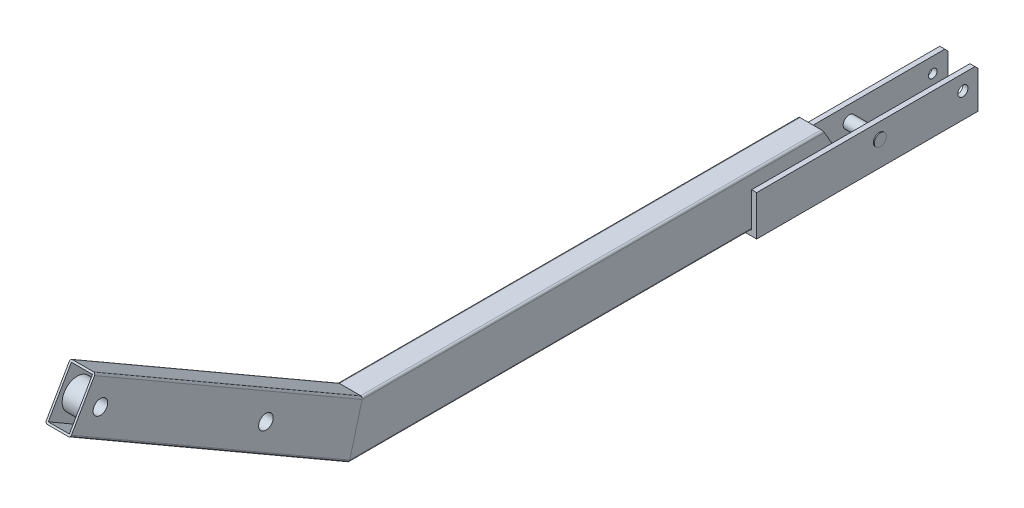
SolidWorks part; units mm, degrees
material "Structural Steel"
ref_plane "Piano frontale" through (0, 0, 0) normal (0, 0, 1) x (1, 0, 0)
ref_plane "Piano superiore" through (0, 0, 0) normal (0, 1, 0) x (1, 0, 0)
ref_plane "Piano destro" through (0, 0, 0) normal (1, 0, 0) x (0, 0, -1)
sketch "Schizzo1" plane through (0, 0, 0) normal (0, 0, 1) x (1, 0, 0)
  line L1 (2, 0) -> (23, 0)
  line L2 (0, 2) -> (0, 48)
  line L3 (2, 50) -> (23, 50)
  line L4 (25, 2) -> (25, 48)
  arc A0 (2, 0) -> (0, 2) centre (2, 2) cw
  arc A1 (23, 0) -> (25, 2) centre (23, 2) ccw
  arc A2 (23, 50) -> (25, 48) centre (23, 48) cw
  arc A3 (0, 48) -> (2, 50) centre (2, 48) cw
  point P7 (0, 0)
  point P10 (25, 0)
  point P15 (0, 50)
  dimension "D3" = 2
  dimension "D1" = 25
  dimension "D2" = 50
extrude "Estrusione-Sottile1" add sketch "Schizzo1" along normal blind 500 thin thin type one direction reverse wall 2
sketch "Schizzo2" plane through (25, 0, 0) normal (1, 0, 0) x (0, 0, -1)
  line L0 (-500, 0) -> (-500, 50)
  line L1 (-500, 50) -> (-486.6025, 50)
  line L2 (-500, 50) -> (0, 50) construction
  line L3 (-486.6025, 50) -> (-500, 0)
  dimension "D1" = 15
extrude "Taglio-Estrusione1" cut sketch "Schizzo2" against normal through all
sketch "Schizzo3" plane through (0, 50, 0) normal (0, 1, 0) x (1, 0, 0)
  line L0 (23, 0) -> (2, 0) construction
  line L1 (5, 0) -> (20, 0)
  line L2 (5, 0) -> (5, -10)
  line L3 (5, -10) -> (20, -10)
  line L4 (20, 0) -> (20, -10)
  line L5 (0, -487.1384) -> (0, 0) construction
  dimension "D1" = 15
  dimension "D2" = 5
  dimension "D3" = 10
extrude "Estrusione-Estrusione1" [suppressed] add sketch "Schizzo3" against normal blind 4 from offset 2 offset against normal yes
sketch "Schizzo4" plane through (0, 50, 0) normal (0, 1, 0) x (1, 0, 0)
  line L0 (0, -487.1384) -> (0, 0) construction
  line L1 (2.5, -290) -> (22.5, -290)
  line L2 (2.5, -290) -> (2.5, -310)
  line L3 (2.5, -310) -> (22.5, -310)
  line L4 (22.5, -290) -> (22.5, -310)
  line L5 (23, 0) -> (2, 0) construction
  dimension "D1" = 2.5
  dimension "D2" = 20
  dimension "D3" = 20
  dimension "D4" = 290
extrude "Estrusione-Estrusione2" [suppressed] add sketch "Schizzo4" along normal blind 20
sketch "Schizzo5" plane through (0, 0, 0) normal (0, 0, -1) x (-1, 0, 0)
  line L0 (0, 0) -> (0, 35)
  line L1 (0, 48) -> (0, 2) construction
  line L2 (0, 0) -> (-25, 0)
  line L3 (-25, 0) -> (-25, 35)
  line L4 (-25, 2) -> (-25, 48) construction
  dimension "D1" = 35
  dimension "D2" = 25
  dimension "D3" = 35
extrude "Estrusione-Sottile2" add sketch "Schizzo5" along normal blind 120 and the other way blind 100 thin thin type one direction reverse wall 5
sketch "Schizzo6" plane through (30, 0, 0) normal (1, 0, 0) x (0, 0, -1)
  line L0 (-100, 35) -> (120, 35) construction
  line L1 (0, 35) -> (0, 48) construction
  circle A0 centre (22, 20) radius 6
  dimension "D1" = 12
  dimension "D2" = 15
  dimension "D3" = 22
extrude "Estrusione-Estrusione3" add sketch "Schizzo6" against normal blind 36 and the other way blind 1
sketch "Schizzo7" plane through (30, 0, 0) normal (1, 0, 0) x (0, 0, -1)
  line L0 (-100, 35) -> (120, 35) construction
  line L1 (120, -5) -> (120, 35) construction
  circle A0 centre (105, 20) radius 5
  dimension "D1" = 10
  dimension "D2" = 15
  dimension "D3" = 15
extrude "Taglio-Estrusione2" cut sketch "Schizzo7" against normal blind 10
chamfer "Smusso1" distance 3 angle 45 2 edges at (-2.5, 35, -120) (27.5, 35, -120)
sketch "Schizzo8" plane through (25, 0, 0) normal (1, 0, 0) x (0, 0, -1)
  line L0 (0, 0) -> (-28.8675, 50)
  line L1 (-486.6025, 50) -> (0, 50) construction
  line L2 (-28.8675, 50) -> (0, 50)
  line L3 (0, 50) -> (0, 0)
  dimension "D1" = 30
extrude "Taglio-Estrusione3" cut sketch "Schizzo8" against normal blind 25
hole_wizard "M10 Tapped Hole1" positions "Sketch1" profile "Sketch2" tap size "M10" standard "ISO"
sketch "Sketch1" plane through (-5, 0, 0) normal (-1, 0, 0) x (0, 0, 1)
  point P0 (-105, 20)
sketch "Sketch2" plane through (-5, 20, -105) normal (0, 1, 0) x (0, 0, 1)
  line L0 (0, 0) -> (0, 30.0537)
  line L1 (0, 30.0537) -> (4.25, 27.5)
  line L2 (4.25, 27.5) -> (4.25, 0)
  line L5 (4.25, 0) -> (0, 0)
  line L10 (0, 30.0537) -> (-4.25, 27.5) construction
  line L11 (0, -6.35) -> (0, 107.95) construction
  dimension "Tap Drill Dia." = 8.5
  dimension "Tap Drill Depth" = 27.5
  dimension "Drill Angle" = 118
cosmetic thread "Filettatura del foro1" parameters "D1"=20, "D2"=10
ref_plane "Piano1" through (12.5, 0, 0) normal (1, 0, 0) x (0, 0, -1)
sketch "Schizzo11" plane through (12.5, 0, 0) normal (1, 0, 0) x (0, 0, -1)
  line L0 (-493.3013, 25) -> (-777.9786, 189.3585) construction
  line L1 (-499.4641, 2) -> (-487.1384, 48) construction
  line L2 (-493.3013, 25) -> (-424.64, 25) construction
  line L3 (-777.1281, 160) -> (-752.1281, 203.3013)
  line L4 (-777.1281, 160) -> (-500, 0)
  line L5 (-752.1281, 203.3013) -> (-486.6025, 50)
  line L6 (-486.6025, 50) -> (-500, 0)
  point P9 (-764.6281, 181.6506)
  dimension "D1" = 150
  dimension "D2" = 320
extrude "Estrusione-Estrusione5" add sketch "Schizzo11" along normal mid plane 25 separate body
fillet "Raccordo1" radius 2 4 edges at (0, 80, 638.5641) (25, 80, 638.5641) (0, 126.6506, 619.3653) (25, 126.6506, 619.3653)
sketch "Schizzo12" plane through (0, 376.5064, 652.1281) normal (0, 0.5, 0.866) x (1, 0, 0)
  line L0 (25, -202) -> (25, -248) construction
  line L1 (2, -248) -> (23, -248)
  line L2 (2, -248) -> (2, -202)
  line L3 (2, -202) -> (23, -202)
  line L4 (23, -248) -> (23, -202)
  line L5 (2, -248) -> (23, -202) construction
  line L6 (2, -202) -> (23, -248) construction
  line L7 (0, -202) -> (0, -248) construction
  line L8 (23, -200) -> (2, -200) construction
  line L9 (23, -250) -> (2, -250) construction
  point P0 (12.5, -225)
  dimension "D1" = 2
  dimension "D2" = 2
  dimension "D3" = 2
  dimension "D4" = 2
extrude "Taglio-Estrusione4" cut sketch "Schizzo12" against normal through all
sketch "Schizzo13" plane through (12.5, 0, 0) normal (1, 0, 0) x (0, 0, -1)
  line L0 (-493.3013, 25) -> (-777.9786, 189.3585) construction
  line L1 (-777.1281, 160) -> (-752.1281, 203.3013) construction
  circle A0 centre (-747.3076, 171.6506) radius 7.25
  circle A1 centre (-582.7628, 76.6506) radius 7.25
  dimension "D1" = 210
  dimension "D2" = 190
  dimension "D3" = 14.5
extrude "Taglio-Estrusione5" cut sketch "Schizzo13" against normal through all both and the other way through all
sketch "Schizzo14" plane through (12.5, 0, 0) normal (1, 0, 0) x (0, 0, -1)
  circle A0 centre (-582.7628, 76.6506) radius 7.25 construction
  circle A1 centre (-747.3076, 171.6506) radius 7.25 construction
  circle A2 centre (-582.7628, 76.6506) radius 7.25
  circle A3 centre (-747.3076, 171.6506) radius 7.25
  circle A4 centre (-747.3076, 171.6506) radius 15
  circle A5 centre (-582.7628, 76.6506) radius 15
  dimension "D1" = 30
extrude "Estrusione-Estrusione6" add sketch "Schizzo14" against normal up to surface and the other way up to surface up to face at (2, 171.6506, 754.5576) other way up to face at (23, 171.6506, 740.0576)
